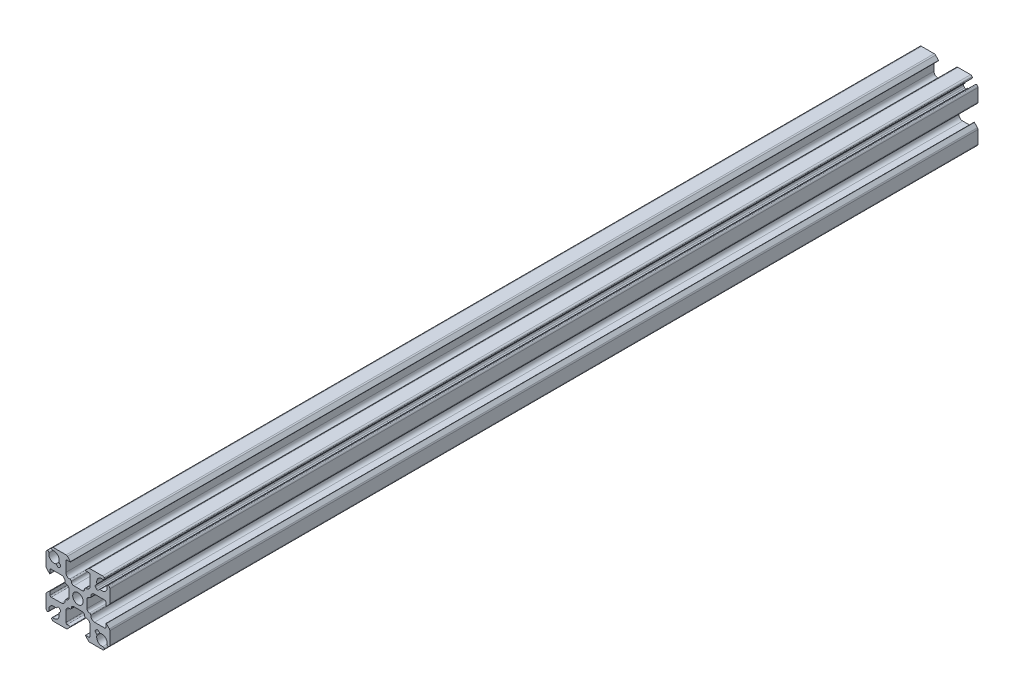
SolidWorks part; units mm, degrees
ref_plane "Front Plane" through (0, 0, 0) normal (0, 0, 1) x (1, 0, 0)
ref_plane "Top Plane" through (0, 0, 0) normal (0, 1, 0) x (1, 0, 0)
ref_plane "Right Plane" through (0, 0, 0) normal (1, 0, 0) x (0, 0, -1)
ref_plane "Plane1" through (0, 0, 0) normal (0, 0, -1) x (-1, 0, 0)
sketch "Sketch1" plane through (0, 0, 0) normal (0, 0, -1) x (-1, 0, 0)
  line L0 (-7.4885, 8.6199) -> (-6.9856, 8.117)
  line L1 (-6.9856, 7.4099) -> (-7.4099, 6.9856)
  line L2 (-8.117, 6.9856) -> (-8.6199, 7.4885)
  line L3 (-12.7, 9.7594) -> (-12.7, 4.7107)
  line L4 (-12.4803, 4.1803) -> (-11.2707, 2.9707)
  line L5 (-11.1, 3.0414) -> (-11.1, 4.325)
  line L6 (-10.6, 4.825) -> (-6.6, 4.825)
  line L7 (-5.1, 3.325) -> (-5.1, 3.15)
  line L8 (-3.6, 1.65) -> (-3.6, -1.65)
  line L9 (-5.1, -3.15) -> (-5.1, -3.325)
  line L10 (-6.6, -4.825) -> (-10.6, -4.825)
  line L11 (-11.1, -4.325) -> (-11.1, -3.0414)
  line L12 (-11.2707, -2.9707) -> (-12.4803, -4.1803)
  line L13 (-12.7, -4.7107) -> (-12.7, -9.7594)
  line L14 (-8.6199, -7.4885) -> (-8.117, -6.9856)
  line L15 (-7.4099, -6.9856) -> (-6.9856, -7.4099)
  line L16 (-6.9856, -8.117) -> (-7.4885, -8.6199)
  line L17 (-9.7594, -12.7) -> (-4.7107, -12.7)
  line L18 (-4.1803, -12.4803) -> (-2.9707, -11.2707)
  line L19 (-3.0414, -11.1) -> (-4.325, -11.1)
  line L20 (-4.825, -10.6) -> (-4.825, -6.6)
  line L21 (-3.325, -5.1) -> (-3.15, -5.1)
  line L22 (-1.65, -3.6) -> (1.65, -3.6)
  line L23 (3.15, -5.1) -> (3.325, -5.1)
  line L24 (4.825, -6.6) -> (4.825, -10.6)
  line L25 (4.325, -11.1) -> (3.0414, -11.1)
  line L26 (2.9707, -11.2707) -> (4.1803, -12.4803)
  line L27 (4.7107, -12.7) -> (9.7594, -12.7)
  line L28 (7.4885, -8.6199) -> (6.9856, -8.117)
  line L29 (6.9856, -7.4099) -> (7.4099, -6.9856)
  line L30 (8.117, -6.9856) -> (8.6199, -7.4885)
  line L31 (12.7, -9.7594) -> (12.7, -4.7107)
  line L32 (12.4803, -4.1803) -> (11.2707, -2.9707)
  line L33 (11.1, -3.0414) -> (11.1, -4.325)
  line L34 (10.6, -4.825) -> (6.6, -4.825)
  line L35 (5.1, -3.325) -> (5.1, -3.15)
  line L36 (3.6, -1.65) -> (3.6, 1.65)
  line L37 (5.1, 3.15) -> (5.1, 3.325)
  line L38 (6.6, 4.825) -> (10.6, 4.825)
  line L39 (11.1, 4.325) -> (11.1, 3.0414)
  line L40 (11.2707, 2.9707) -> (12.4803, 4.1803)
  line L41 (12.7, 4.7107) -> (12.7, 9.7594)
  line L42 (8.6199, 7.4885) -> (8.117, 6.9856)
  line L43 (7.4099, 6.9856) -> (6.9856, 7.4099)
  line L44 (6.9856, 8.117) -> (7.4885, 8.6199)
  line L45 (9.7594, 12.7) -> (4.7107, 12.7)
  line L46 (4.1803, 12.4803) -> (2.9707, 11.2707)
  line L47 (3.0414, 11.1) -> (4.325, 11.1)
  line L48 (4.825, 10.6) -> (4.825, 6.6)
  line L49 (3.325, 5.1) -> (3.15, 5.1)
  line L50 (1.65, 3.6) -> (-1.65, 3.6)
  line L51 (-3.15, 5.1) -> (-3.325, 5.1)
  line L52 (-4.825, 6.6) -> (-4.825, 10.6)
  line L53 (-4.325, 11.1) -> (-3.0414, 11.1)
  line L54 (-2.9707, 11.2707) -> (-4.1803, 12.4803)
  line L55 (-4.7107, 12.7) -> (-9.7594, 12.7)
  circle A0 centre (0, 0) radius 2.08
  arc A1 (-9.7594, 12.7) -> (-10.4266, 12.2927) centre (-9.7594, 11.95) ccw
  arc A2 (-10.4266, 12.2927) -> (-9.8933, 11.5721) centre (-9.9818, 12.0642) ccw
  arc A3 (-9.8933, 11.5721) -> (-7.5492, 8.8748) centre (-9.525, 9.525) cw
  arc A4 (-7.5492, 8.8748) -> (-7.4885, 8.6199) centre (-7.3118, 8.7967) ccw
  arc A5 (-6.9856, 8.117) -> (-6.9856, 7.4099) centre (-7.3392, 7.7635) cw
  arc A6 (-7.4099, 6.9856) -> (-8.117, 6.9856) centre (-7.7635, 7.3392) cw
  arc A7 (-8.6199, 7.4885) -> (-8.8748, 7.5492) centre (-8.7967, 7.3118) ccw
  arc A8 (-8.8748, 7.5492) -> (-11.5721, 9.8933) centre (-9.525, 9.525) cw
  arc A9 (-11.5721, 9.8933) -> (-12.2927, 10.4266) centre (-12.0642, 9.9818) ccw
  arc A10 (-12.2927, 10.4266) -> (-12.7, 9.7594) centre (-11.95, 9.7594) ccw
  arc A11 (-12.7, 4.7107) -> (-12.4803, 4.1803) centre (-11.95, 4.7107) ccw
  arc A12 (-11.2707, 2.9707) -> (-11.1, 3.0414) centre (-11.2, 3.0414) ccw
  arc A13 (-11.1, 4.325) -> (-10.6, 4.825) centre (-10.6, 4.325) cw
  arc A14 (-6.6, 4.825) -> (-5.1, 3.325) centre (-6.6, 3.325) cw
  arc A15 (-5.1, 3.15) -> (-4.6, 2.65) centre (-4.6, 3.15) ccw
  arc A16 (-4.6, 2.65) -> (-3.6, 1.65) centre (-4.6, 1.65) cw
  arc A17 (-3.6, -1.65) -> (-4.6, -2.65) centre (-4.6, -1.65) cw
  arc A18 (-4.6, -2.65) -> (-5.1, -3.15) centre (-4.6, -3.15) ccw
  arc A19 (-5.1, -3.325) -> (-6.6, -4.825) centre (-6.6, -3.325) cw
  arc A20 (-10.6, -4.825) -> (-11.1, -4.325) centre (-10.6, -4.325) cw
  arc A21 (-11.1, -3.0414) -> (-11.2707, -2.9707) centre (-11.2, -3.0414) ccw
  arc A22 (-12.4803, -4.1803) -> (-12.7, -4.7107) centre (-11.95, -4.7107) ccw
  arc A23 (-12.7, -9.7594) -> (-12.2927, -10.4266) centre (-11.95, -9.7594) ccw
  arc A24 (-12.2927, -10.4266) -> (-11.5721, -9.8933) centre (-12.0642, -9.9818) ccw
  arc A25 (-11.5721, -9.8933) -> (-8.8748, -7.5492) centre (-9.525, -9.525) cw
  arc A26 (-8.8748, -7.5492) -> (-8.6199, -7.4885) centre (-8.7967, -7.3118) ccw
  arc A27 (-8.117, -6.9856) -> (-7.4099, -6.9856) centre (-7.7635, -7.3392) cw
  arc A28 (-6.9856, -7.4099) -> (-6.9856, -8.117) centre (-7.3392, -7.7635) cw
  arc A29 (-7.4885, -8.6199) -> (-7.5492, -8.8748) centre (-7.3118, -8.7967) ccw
  arc A30 (-7.5492, -8.8748) -> (-9.8933, -11.5721) centre (-9.525, -9.525) cw
  arc A31 (-9.8933, -11.5721) -> (-10.4266, -12.2927) centre (-9.9818, -12.0642) ccw
  arc A32 (-10.4266, -12.2927) -> (-9.7594, -12.7) centre (-9.7594, -11.95) ccw
  arc A33 (-4.7107, -12.7) -> (-4.1803, -12.4803) centre (-4.7107, -11.95) ccw
  arc A34 (-2.9707, -11.2707) -> (-3.0414, -11.1) centre (-3.0414, -11.2) ccw
  arc A35 (-4.325, -11.1) -> (-4.825, -10.6) centre (-4.325, -10.6) cw
  arc A36 (-4.825, -6.6) -> (-3.325, -5.1) centre (-3.325, -6.6) cw
  arc A37 (-3.15, -5.1) -> (-2.65, -4.6) centre (-3.15, -4.6) ccw
  arc A38 (-2.65, -4.6) -> (-1.65, -3.6) centre (-1.65, -4.6) cw
  arc A39 (1.65, -3.6) -> (2.65, -4.6) centre (1.65, -4.6) cw
  arc A40 (2.65, -4.6) -> (3.15, -5.1) centre (3.15, -4.6) ccw
  arc A41 (3.325, -5.1) -> (4.825, -6.6) centre (3.325, -6.6) cw
  arc A42 (4.825, -10.6) -> (4.325, -11.1) centre (4.325, -10.6) cw
  arc A43 (3.0414, -11.1) -> (2.9707, -11.2707) centre (3.0414, -11.2) ccw
  arc A44 (4.1803, -12.4803) -> (4.7107, -12.7) centre (4.7107, -11.95) ccw
  arc A45 (9.7594, -12.7) -> (10.4266, -12.2927) centre (9.7594, -11.95) ccw
  arc A46 (10.4266, -12.2927) -> (9.8933, -11.5721) centre (9.9818, -12.0642) ccw
  arc A47 (9.8933, -11.5721) -> (7.5492, -8.8748) centre (9.525, -9.525) cw
  arc A48 (7.5492, -8.8748) -> (7.4885, -8.6199) centre (7.3118, -8.7967) ccw
  arc A49 (6.9856, -8.117) -> (6.9856, -7.4099) centre (7.3392, -7.7635) cw
  arc A50 (7.4099, -6.9856) -> (8.117, -6.9856) centre (7.7635, -7.3392) cw
  arc A51 (8.6199, -7.4885) -> (8.8748, -7.5492) centre (8.7967, -7.3118) ccw
  arc A52 (8.8748, -7.5492) -> (11.5721, -9.8933) centre (9.525, -9.525) cw
  arc A53 (11.5721, -9.8933) -> (12.2927, -10.4266) centre (12.0642, -9.9818) ccw
  arc A54 (12.2927, -10.4266) -> (12.7, -9.7594) centre (11.95, -9.7594) ccw
  arc A55 (12.7, -4.7107) -> (12.4803, -4.1803) centre (11.95, -4.7107) ccw
  arc A56 (11.2707, -2.9707) -> (11.1, -3.0414) centre (11.2, -3.0414) ccw
  arc A57 (11.1, -4.325) -> (10.6, -4.825) centre (10.6, -4.325) cw
  arc A58 (6.6, -4.825) -> (5.1, -3.325) centre (6.6, -3.325) cw
  arc A59 (5.1, -3.15) -> (4.6, -2.65) centre (4.6, -3.15) ccw
  arc A60 (4.6, -2.65) -> (3.6, -1.65) centre (4.6, -1.65) cw
  arc A61 (3.6, 1.65) -> (4.6, 2.65) centre (4.6, 1.65) cw
  arc A62 (4.6, 2.65) -> (5.1, 3.15) centre (4.6, 3.15) ccw
  arc A63 (5.1, 3.325) -> (6.6, 4.825) centre (6.6, 3.325) cw
  arc A64 (10.6, 4.825) -> (11.1, 4.325) centre (10.6, 4.325) cw
  arc A65 (11.1, 3.0414) -> (11.2707, 2.9707) centre (11.2, 3.0414) ccw
  arc A66 (12.4803, 4.1803) -> (12.7, 4.7107) centre (11.95, 4.7107) ccw
  arc A67 (12.7, 9.7594) -> (12.2927, 10.4266) centre (11.95, 9.7594) ccw
  arc A68 (12.2927, 10.4266) -> (11.5721, 9.8933) centre (12.0642, 9.9818) ccw
  arc A69 (11.5721, 9.8933) -> (8.8748, 7.5492) centre (9.525, 9.525) cw
  arc A70 (8.8748, 7.5492) -> (8.6199, 7.4885) centre (8.7967, 7.3118) ccw
  arc A71 (8.117, 6.9856) -> (7.4099, 6.9856) centre (7.7635, 7.3392) cw
  arc A72 (6.9856, 7.4099) -> (6.9856, 8.117) centre (7.3392, 7.7635) cw
  arc A73 (7.4885, 8.6199) -> (7.5492, 8.8748) centre (7.3118, 8.7967) ccw
  arc A74 (7.5492, 8.8748) -> (9.8933, 11.5721) centre (9.525, 9.525) cw
  arc A75 (9.8933, 11.5721) -> (10.4266, 12.2927) centre (9.9818, 12.0642) ccw
  arc A76 (10.4266, 12.2927) -> (9.7594, 12.7) centre (9.7594, 11.95) ccw
  arc A77 (4.7107, 12.7) -> (4.1803, 12.4803) centre (4.7107, 11.95) ccw
  arc A78 (2.9707, 11.2707) -> (3.0414, 11.1) centre (3.0414, 11.2) ccw
  arc A79 (4.325, 11.1) -> (4.825, 10.6) centre (4.325, 10.6) cw
  arc A80 (4.825, 6.6) -> (3.325, 5.1) centre (3.325, 6.6) cw
  arc A81 (3.15, 5.1) -> (2.65, 4.6) centre (3.15, 4.6) ccw
  arc A82 (2.65, 4.6) -> (1.65, 3.6) centre (1.65, 4.6) cw
  arc A83 (-1.65, 3.6) -> (-2.65, 4.6) centre (-1.65, 4.6) cw
  arc A84 (-2.65, 4.6) -> (-3.15, 5.1) centre (-3.15, 4.6) ccw
  arc A85 (-3.325, 5.1) -> (-4.825, 6.6) centre (-3.325, 6.6) cw
  arc A86 (-4.825, 10.6) -> (-4.325, 11.1) centre (-4.325, 10.6) cw
  arc A87 (-3.0414, 11.1) -> (-2.9707, 11.2707) centre (-3.0414, 11.2) ccw
  arc A88 (-4.1803, 12.4803) -> (-4.7107, 12.7) centre (-4.7107, 11.95) ccw
extrude "Boss-Extrude1" add sketch "Sketch1" against normal mid plane 345.1098
hole_wizard "Ø6.4 (6.4) Diameter Hole1" positions "Sketch3" profile "Sketch2" hole size "Ø6.4" standard "ANSI Metric" end condition through all
sketch "Sketch3" plane through (3.6, 0, 0) normal (1, 0, 0) x (0, 0, -1)
  point P0 (-132.5549, 0)
  point P3 (-12.5549, 0)
  point P6 (107.4451, 0)
sketch "Sketch2" plane through (3.6, 0, 132.5549) normal (0, 1, 0) x (0, 0, -1)
  line L0 (0, 0) -> (0, 16.3)
  line L1 (0, 16.3) -> (3.2, 16.3)
  line L2 (3.2, 16.3) -> (3.2, 0)
  line L5 (3.2, 0) -> (0, 0)
  line L11 (0, -6.35) -> (0, 107.95) construction
  dimension "Thru Hole Dia." = 6.4
  dimension "Thru Hole Depth" = 16.3
